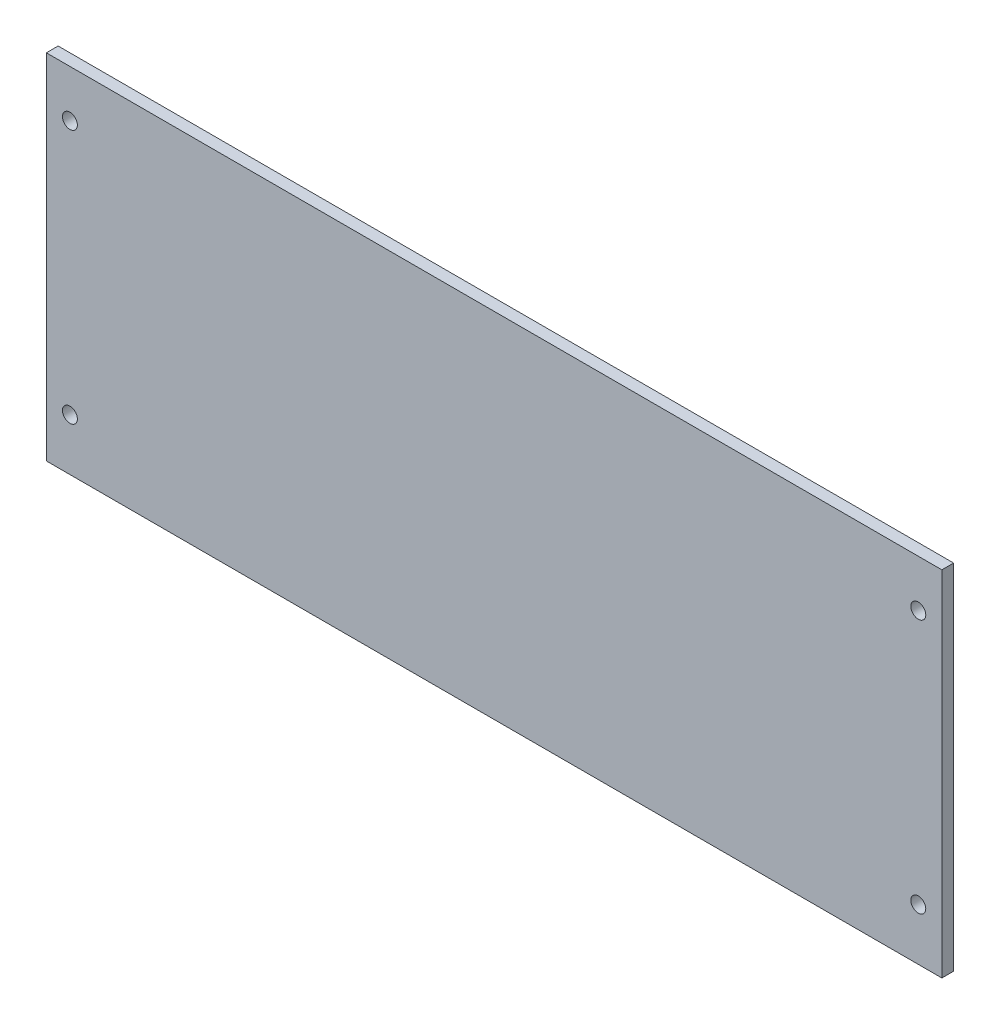
SolidWorks part; units mm, degrees
ref_plane "Alzado" through (0, 0, 0) normal (0, 0, 1) x (1, 0, 0)
ref_plane "Planta" through (0, 0, 0) normal (0, 1, 0) x (1, 0, 0)
ref_plane "Vista lateral" through (0, 0, 0) normal (1, 0, 0) x (0, 0, -1)
sketch "Sketch1" plane through (0, 0, 0) normal (0, 0, 1) x (1, 0, 0)
  line L1 (0, 0) -> (190, 0)
  line L2 (0, 0) -> (0, 75)
  line L3 (0, 75) -> (190, 75)
  line L4 (190, 0) -> (190, 75)
  circle A0 centre (5, 65) radius 1.585
  circle A1 centre (185, 65) radius 1.585
  circle A2 centre (5, 11) radius 1.585
  circle A3 centre (185, 11) radius 1.585
  point P12 (0, 0)
  point P13 (0, 0)
  dimension "D3" = 3.17
  dimension "D4" = 3.17
  dimension "D10" = 3.17
  dimension "D14" = 3.17
  dimension "190" = 190
  dimension "D2" = 5
  dimension "D5" = 5
  dimension "D6" = 10
  dimension "D7" = 10
  dimension "D8" = 180
  dimension "D9" = 54
  dimension "D11" = 5
  dimension "D12" = 11
  dimension "D13" = 11
  dimension "D15" = 5
  dimension "D16" = 54
extrude "Boss-Extrude1" add sketch "Sketch1" along normal blind 2.5
equation "\"0.5.00mm\"=1"
